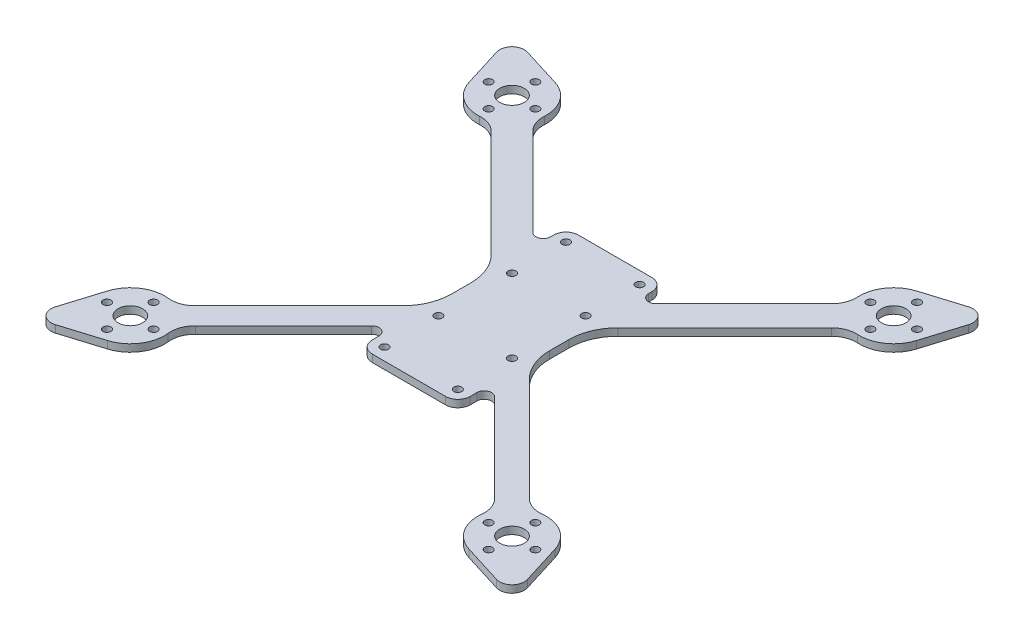
SolidWorks part; units mm, degrees
ref_plane "Front Plane" through (0, 0, 0) normal (0, 0, 1) x (1, 0, 0)
ref_plane "Top Plane" through (0, 0, 0) normal (0, 1, 0) x (1, 0, 0)
ref_plane "Right Plane" through (0, 0, 0) normal (1, 0, 0) x (0, 0, -1)
sketch "Sketch1" plane through (0, 0, 0) normal (0, 1, 0) x (1, 0, 0)
  line L0 (0, 110) -> (0, -110) construction
  line L4 (-15, 42) -> (15, 42)
  line L6 (-14.9441, -42) -> (14.9441, -42)
  line L7 (20, 3.2304) -> (20, -4.6447)
  line L8 (-15, 15) -> (15, 15) construction
  line L10 (-15, -15) -> (15, -15) construction
  line L11 (15, 15) -> (15, -15) construction
  line L12 (25.1213, 33.6066) -> (60.89, 69.3753)
  line L13 (25.8579, 17.3726) -> (69.3753, 60.89)
  line L14 (25.0654, -32.1365) -> (60.9986, -68.0696)
  line L15 (25.8579, -18.7868) -> (68.0696, -60.9986)
  line L16 (77.7817, 77.7817) -> (98.9949, 98.9949) construction
  line L17 (77.7817, -77.7817) -> (98.9949, -98.9949) construction
  line L18 (73.6461, -91.157) -> (89.9418, -96.1957)
  line L19 (96.1957, -89.9418) -> (91.157, -73.6461)
  line L20 (89.9418, 96.1957) -> (73.6461, 91.157)
  line L21 (96.1957, 89.9418) -> (91.157, 73.6461)
  line L22 (0, 0) -> (77.7817, 77.7817) construction
  line L23 (20, 37) -> (20, 35.7279)
  line L24 (0, 0) -> (77.7817, -77.7817) construction
  line L35 (-20, 0) -> (20, 0) construction
  line L37 (19.9441, -34.2578) -> (19.9441, -37)
  line L39 (0, 0) -> (-77.7817, -77.7817) construction
  line L40 (0, 0) -> (-77.7817, 77.7817) construction
  line L41 (-77.7817, -77.7817) -> (-98.9949, -98.9949) construction
  line L42 (-77.7817, 77.7817) -> (-98.9949, 98.9949) construction
  line L43 (-15, 15) -> (-15, -15) construction
  line L46 (-19.9441, -34.2578) -> (-19.9441, -37)
  line L47 (-20, 37) -> (-20, 35.7279)
  line L48 (-96.1957, 89.9418) -> (-91.157, 73.6461)
  line L49 (-89.9418, 96.1957) -> (-73.6461, 91.157)
  line L50 (-96.1957, -89.9418) -> (-91.157, -73.6461)
  line L51 (-73.6461, -91.157) -> (-89.9418, -96.1957)
  line L52 (-25.8579, -18.7868) -> (-68.0696, -60.9986)
  line L53 (-25.0654, -32.1365) -> (-60.9986, -68.0696)
  line L54 (-25.8579, 17.3726) -> (-69.3753, 60.89)
  line L55 (-25.1213, 33.6066) -> (-60.89, 69.3753)
  line L56 (-20, 3.2304) -> (-20, -4.6447)
  circle A1 centre (77.7817, 77.7817) radius 63.5 construction
  circle A2 centre (77.7817, -77.7817) radius 63.5 construction
  circle A5 centre (77.7817, 77.7817) radius 9.5 construction
  circle A9 centre (77.7817, 68.2817) radius 1.6
  circle A10 centre (68.2817, 77.7817) radius 1.6
  circle A11 centre (77.7817, 87.2817) radius 1.6
  circle A12 centre (87.2817, 77.7817) radius 1.6
  circle A13 centre (77.7817, -87.2817) radius 1.6
  circle A14 centre (77.7817, -77.7817) radius 9.5 construction
  circle A15 centre (68.2817, -77.7817) radius 1.6
  circle A16 centre (77.7817, -68.2817) radius 1.6
  circle A17 centre (87.2817, -77.7817) radius 1.6
  arc A28 (77.0028, 63.8034) -> (91.157, 73.6461) centre (77.7817, 77.7817) ccw
  arc A29 (63.8668, -76.2411) -> (73.6461, -91.157) centre (77.7817, -77.7817) ccw
  arc A30 (73.6461, 91.157) -> (63.8034, 77.0028) centre (77.7817, 77.7817) ccw
  arc A31 (91.157, -73.6461) -> (76.2411, -63.8668) centre (77.7817, -77.7817) ccw
  arc A36 (96.1957, 89.9418) -> (89.9418, 96.1957) centre (91.4188, 91.4188) ccw
  arc A37 (96.1957, -89.9418) -> (89.9418, -96.1957) centre (91.4188, -91.4188) cw
  circle A42 centre (15, 15) radius 1.6
  circle A43 centre (15, -15) radius 1.6
  circle A44 centre (77.7817, 77.7817) radius 5
  circle A45 centre (77.7817, -77.7817) radius 5
  circle A47 centre (0, 0) radius 110 construction
  circle A49 centre (-87.2817, -77.7817) radius 1.6 [skipped]
  circle A50 centre (-77.7817, -68.2817) radius 1.6 [skipped]
  circle A51 centre (-68.2817, -77.7817) radius 1.6 [skipped]
  circle A52 centre (-77.7817, -87.2817) radius 1.6 [skipped]
  circle A53 centre (-77.7817, 87.2817) radius 1.6 [skipped]
  circle A54 centre (-68.2817, 77.7817) radius 1.6 [skipped]
  circle A55 centre (-77.7817, 68.2817) radius 1.6 [skipped]
  circle A56 centre (-87.2817, 77.7817) radius 1.6 [skipped]
  circle A57 centre (-77.7817, -77.7817) radius 9.5 construction
  circle A58 centre (-77.7817, 77.7817) radius 9.5 construction
  circle A91 centre (14.9441, -37) radius 1.6
  circle A92 centre (15, 37) radius 1.6
  arc A97 (60.89, 69.3753) -> (63.8034, 77.0028) centre (53.8189, 76.4463) ccw
  arc A98 (69.3753, 60.89) -> (77.0028, 63.8034) centre (76.4463, 53.8189) cw
  arc A99 (63.8668, -76.2411) -> (60.9986, -68.0696) centre (53.9275, -75.1407) ccw
  arc A100 (68.0696, -60.9986) -> (76.2411, -63.8668) centre (75.1407, -53.9275) ccw
  circle A103 centre (-77.7817, -77.7817) radius 9.5 construction
  circle A104 centre (-77.7817, 77.7817) radius 9.5 construction
  circle A105 centre (-77.7817, -77.7817) radius 63.5 construction
  circle A106 centre (-77.7817, 77.7817) radius 63.5 construction
  arc A107 (-68.0696, -60.9986) -> (-76.2411, -63.8668) centre (-75.1407, -53.9275) cw
  arc A108 (-63.8668, -76.2411) -> (-60.9986, -68.0696) centre (-53.9275, -75.1407) cw
  arc A109 (-69.3753, 60.89) -> (-77.0028, 63.8034) centre (-76.4463, 53.8189) ccw
  arc A110 (-60.89, 69.3753) -> (-63.8034, 77.0028) centre (-53.8189, 76.4463) cw
  circle A111 centre (-15, 37) radius 1.6
  circle A112 centre (-14.9441, -37) radius 1.6
  circle A113 centre (-77.7817, -77.7817) radius 5
  circle A114 centre (-77.7817, 77.7817) radius 5
  circle A115 centre (-15, -15) radius 1.6
  circle A116 centre (-15, 15) radius 1.6
  arc A117 (-96.1957, -89.9418) -> (-89.9418, -96.1957) centre (-91.4188, -91.4188) ccw
  arc A118 (-96.1957, 89.9418) -> (-89.9418, 96.1957) centre (-91.4188, 91.4188) cw
  arc A119 (-91.157, -73.6461) -> (-76.2411, -63.8668) centre (-77.7817, -77.7817) cw
  arc A120 (-73.6461, 91.157) -> (-63.8034, 77.0028) centre (-77.7817, 77.7817) cw
  arc A121 (-63.8668, -76.2411) -> (-73.6461, -91.157) centre (-77.7817, -77.7817) cw
  arc A122 (-77.0028, 63.8034) -> (-91.157, 73.6461) centre (-77.7817, 77.7817) cw
  circle A123 centre (-87.2817, -77.7817) radius 1.6
  circle A124 centre (-77.7817, -68.2817) radius 1.6
  circle A125 centre (-68.2817, -77.7817) radius 1.6
  circle A126 centre (-77.7817, -87.2817) radius 1.6
  circle A127 centre (-87.2817, 77.7817) radius 1.6
  circle A128 centre (-77.7817, 87.2817) radius 1.6
  circle A129 centre (-68.2817, 77.7817) radius 1.6
  circle A130 centre (-77.7817, 68.2817) radius 1.6
  arc A131 (20, 35.7279) -> (25.1213, 33.6066) centre (23, 35.7279) ccw
  arc A132 (25.0654, -32.1365) -> (19.9441, -34.2578) centre (22.9441, -34.2578) ccw
  arc A133 (-25.8579, -18.7868) -> (-20, -4.6447) centre (-40, -4.6447) ccw
  arc A134 (-25.8579, 17.3726) -> (-20, 3.2304) centre (-40, 3.2304) cw
  arc A135 (25.8579, -18.7868) -> (20, -4.6447) centre (40, -4.6447) cw
  arc A136 (25.8579, 17.3726) -> (20, 3.2304) centre (40, 3.2304) ccw
  arc A137 (-19.9441, -34.2578) -> (-25.0654, -32.1365) centre (-22.9441, -34.2578) ccw
  arc A138 (-20, 35.7279) -> (-25.1213, 33.6066) centre (-23, 35.7279) cw
  arc A139 (-19.9441, -37) -> (-14.9441, -42) centre (-14.9441, -37) ccw
  arc A140 (14.9441, -42) -> (19.9441, -37) centre (14.9441, -37) ccw
  arc A141 (15, 42) -> (20, 37) centre (15, 37) cw
  arc A142 (-20, 37) -> (-15, 42) centre (-15, 37) cw
  point P4 (0, 15)
  point P6 (0, 15)
  point P12 (0, 38)
  point P13 (19.9441, -38)
  point P16 (20, 0)
  point P20 (0, 0)
  point P34 (77.7817, 77.7817)
  point P49 (0, -15)
  point P50 (0, 15)
  point P65 (0, 0)
  point P75 (-77.7817, 77.7817)
  point P76 (0, 42)
  point P80 (0, -15)
  point P89 (0, 38)
  point P93 (0, -15)
  point P160 (0, -38)
  point P165 (0, -42)
  point P168 (20, 28.4853)
  point P171 (19.9441, -27.0152)
  point P178 (-20, -12.9289)
  point P180 (0, -38)
  point P182 (-20, 11.5147)
  point P185 (20, -12.9289)
  point P188 (20, 11.5147)
  point P190 (-19.9441, -27.0152)
  point P193 (-20, 28.4853)
  point P196 (-19.9441, -42)
  point P199 (19.9441, -42)
  point P202 (20, 42)
  point P205 (-20, 42)
  dimension "D3" = 42
  dimension "D9" = 4
  dimension "D13" = 20
  dimension "D17" = 5
  dimension "D18" = 5
  dimension "D5" = 5
  dimension "D6" = 5
  dimension "D7" = 6
  dimension "D8" = 6
  dimension "D11" = 3
  dimension "D12" = 10
  dimension "D14" = 3
  dimension "D2" = 20
  dimension "D4" = 42
  dimension "D15" = 30
  dimension "D16" = 30
  dimension "D10" = 4
extrude "Boss-Extrude1" add sketch "Sketch1" along normal blind 3
